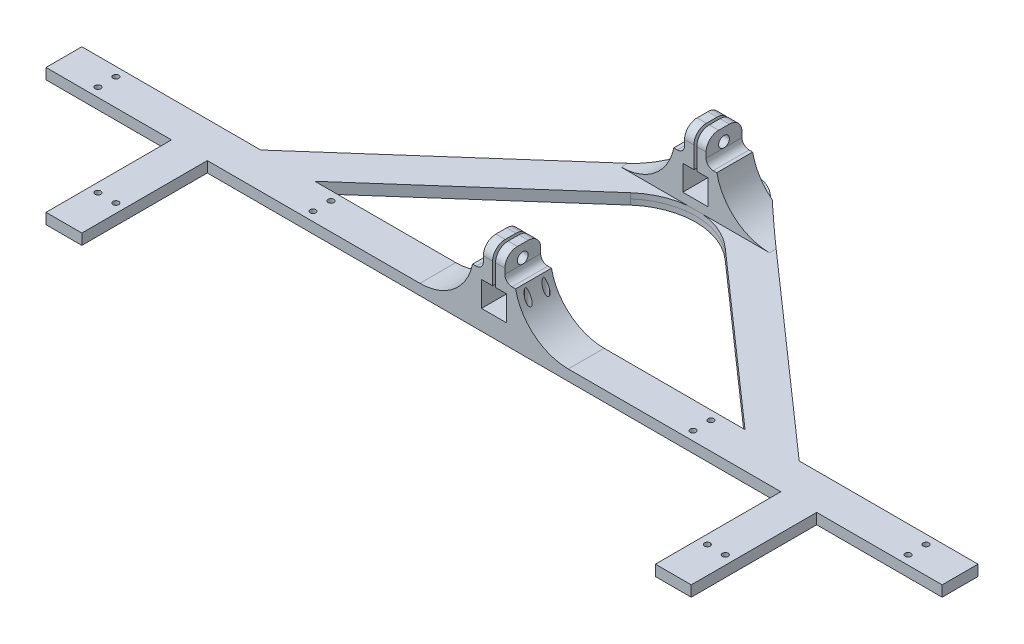
SolidWorks part; units mm, degrees
ref_plane "前视基准面" through (0, 0, 0) normal (0, 0, 1) x (1, 0, 0)
ref_plane "上视基准面" through (0, 0, 0) normal (0, 1, 0) x (1, 0, 0)
ref_plane "右视基准面" through (0, 0, 0) normal (1, 0, 0) x (0, 0, -1)
sketch "草图1" plane through (0, 0, 0) normal (0, 1, 0) x (1, 0, 0)
  line L1 (-125, 5) -> (125, 5)
  line L2 (-125, 5) -> (-125, -5)
  line L3 (-125, -5) -> (125, -5)
  line L4 (125, 5) -> (125, -5)
  line L5 (-125, 5) -> (125, -5) construction
  line L6 (-125, -5) -> (125, 5) construction
  point P0 (0, 0)
  dimension "D1" = 250
  dimension "D2" = 10
extrude "凸台-拉伸1" add sketch "草图1" along normal blind 1.5
sketch "草图22" plane through (0, 0, 0) normal (0, -1, 0) x (1, 0, 0)
  line L0 (0, 107.0541) -> (0, -222.8841) construction
  line L1 (0, 0) -> (-60, 0)
  line L2 (-125, 5) -> (125, 5) construction
  line L4 (125, -5) -> (-125, -5) construction
  line L5 (60, 0) -> (60, -5)
  line L6 (-60, -5) -> (0, -57.915)
  line L7 (0, -57.915) -> (60, -5)
  line L8 (-75.1186, -5) -> (0, -71.2484)
  line L9 (0, -71.2484) -> (75.1186, -5)
  line L10 (-60, -5) -> (-75.1186, -5)
  line L11 (60, -5) -> (75.1186, -5)
  line M16 (-125, -5) -> (125, -5)
  dimension "D1" = 60
  dimension "D2" = 80
  dimension "D3" = 10
extrude "凸台-拉伸10" add sketch "草图22" against normal blind 1.5 separate body contours L0 L6 L8 M16 | L7 L0 L9 M16 region at (33.9206, 0, -34.9152) region at (-33.9206, 0, -34.9152)
fillet "圆角1" radius 10 1 edges at (0, 0.75, -71.2484)
fillet "圆角2" radius 20 1 edges at (0, 0.75, -57.915)
sketch "草图24" plane through (0, 1.5, 0) normal (0, 1, 0) x (1, 0, 0)
  line L1 (-10, 5) -> (10, 5)
  line L2 (-10, 5) -> (-10, -5)
  line L3 (-10, -5) -> (10, -5)
  line L4 (10, 5) -> (10, -5)
  line L5 (-10, 5) -> (10, -5) construction
  line L6 (-10, -5) -> (10, 5) construction
  point P0 (0, 0)
  dimension "D1" = 20
  dimension "D2" = 10
extrude "凸台-拉伸11" add sketch "草图24" along normal blind 20
sketch "草图25" plane through (0, 0, 5) normal (0, 0, 1) x (1, 0, 0)
  line L1 (0, 23.6125) -> (0, -2.2867) construction
sketch "草图26" plane through (0, 1.5, 0) normal (0, 1, 0) x (1, 0, 0)
  line L0 (0, 141.3842) -> (0, -41.294) construction
  line L2 (-11, 61.1419) -> (11, 61.1419)
  line L3 (-11, 61.1419) -> (-11, 51.1419)
  line L4 (-11, 51.1419) -> (11, 51.1419)
  line L5 (11, 61.1419) -> (11, 51.1419)
  line L6 (-11, 61.1419) -> (11, 51.1419) construction
  line L7 (-11, 51.1419) -> (11, 61.1419) construction
  point P6 (0, 56.1419)
  dimension "D1" = 22
  dimension "D2" = 10
sketch "草图41" plane through (0, 0, 5) normal (0, 0, 1) x (1, 0, 0)
  line L0 (125, 0.75) -> (-129.8236, 0.75) construction
  line L1 (125, 1.5) -> (125, 0) construction
  line L2 (125, 0.75) -> (85, 0.75)
  line L4 (80, 1.5) -> (90, 1.5)
  line L5 (80, 1.5) -> (80, 0)
  line L6 (80, 0) -> (90, 0)
  line L7 (90, 1.5) -> (90, 0)
  line L8 (80, 1.5) -> (90, 0) construction
  line L9 (80, 0) -> (90, 1.5) construction
  line M8 (-125, 0) -> (125, 0)
  line M10 (125, 1.5) -> (10, 1.5)
  dimension "D1" = 40
  dimension "D2" = 10
  dimension "D3" = 1.5
extrude "凸台-拉伸13" add sketch "草图41" along normal blind 35 contours L7 L5 M10 M8 region at (85, 1.3989, 5)
sketch "草图42" plane through (0, 0, 5) normal (0, 0, 1) x (1, 0, 0)
  line L0 (-125, 0.75) -> (-85, 0.75)
  line L1 (-125, 1.5) -> (-125, 0) construction
  line L3 (-90, 1.5) -> (-80, 1.5)
  line L4 (-90, 1.5) -> (-90, 0)
  line L5 (-90, 0) -> (-80, 0)
  line L6 (-80, 1.5) -> (-80, 0)
  line L7 (-90, 1.5) -> (-80, 0) construction
  line L8 (-90, 0) -> (-80, 1.5) construction
  line M14 (-10, 1.5) -> (-125, 1.5)
  line M16 (-125, 0) -> (80, 0)
  dimension "D1" = 40
  dimension "D2" = 10
  dimension "D3" = 1.5
extrude "凸台-拉伸14" add sketch "草图42" along normal blind 35 contours L6 L4 M14 M16 region at (-85, 1.3989, 5)
sketch "草图57" plane through (0, 0, 0) normal (0, -1, 0) x (-1, 0, 0)
  line L0 (125, -5) -> (90, -5)
  line L1 (90, -5) -> (90, -40)
  line L2 (90, -40) -> (80, -40)
  line L3 (80, -40) -> (80, -5)
  line L4 (80, -5) -> (-80, -5)
  line L5 (-80, -5) -> (-80, -40)
  line L6 (-80, -40) -> (-90, -40)
  line L7 (-90, -40) -> (-90, -5)
  line L8 (-90, -5) -> (-125, -5)
  line L9 (-125, -5) -> (-125, 5)
  line L10 (-125, 5) -> (-75.1186, 5)
  line L11 (-75.1186, 5) -> (-6.6144, 65.415)
  line L12 (-6.6144, 65.415) -> (0, 71.2484)
  line L13 (0, 71.2484) -> (6.6144, 65.415)
  line L14 (6.6144, 65.415) -> (75.1186, 5)
  line L15 (75.1186, 5) -> (125, 5)
  line L16 (125, 5) -> (125, -5)
  line L17 (60, 5) -> (-60, 5)
  line L18 (-60, 5) -> (0, 57.915)
  line L19 (0, 57.915) -> (60, 5)
extrude "凸台-拉伸15" add sketch "草图57" along normal blind 1.5
fillet "圆角5" radius 20 1 edges at (0, -0.75, -57.915)
fillet "圆角6" radius 10 1 edges at (0, -0.75, -71.2484)
sketch "草图58" plane through (0, -1.5, 0) normal (0, -1, 0) x (1, 0, 0)
  line L0 (0, 12.1149) -> (0, -11.1082) construction
  line L1 (0, 0) -> (7, 0)
  line L2 (7, 0) -> (7, 2.5)
  line L3 (7, 0) -> (7, -2.5)
  line L4 (127.0686, 0) -> (101.0767, 0) construction
  line L5 (125, 0) -> (113, 0)
  line L6 (125, -5) -> (125, 5) construction
  line L7 (113, 0) -> (113, 2.5)
  line L8 (113, 0) -> (113, -2.5)
  line L10 (-125, 5) -> (-125, -5)
  line L11 (125, 5) -> (125, -5)
  line L12 (0, 0) -> (53, 0)
  line L14 (53, 0) -> (53, 2.5)
  line L15 (53, 0) -> (53, -2.5)
  line L16 (-85, 40) -> (-85, 28)
  line L17 (-80, 40) -> (-90, 40) construction
  line L18 (-85, 28) -> (-87.5, 28)
  line L19 (-85, 28) -> (-82.5, 28)
  circle A0 centre (7, -2.5) radius 0.8
  circle A1 centre (7, 2.5) radius 0.8
  circle A2 centre (113, 2.5) radius 0.8
  circle A3 centre (113, -2.5) radius 0.8
  circle A4 centre (-113, -2.5) radius 0.8
  circle A5 centre (-113, 2.5) radius 0.8
  circle A6 centre (53, 2.5) radius 0.8
  circle A7 centre (53, -2.5) radius 0.8
  circle A8 centre (-53, -2.5) radius 0.8
  circle A9 centre (-53, 2.5) radius 0.8
  circle A10 centre (-82.5, 28) radius 0.8
  circle A11 centre (-87.5, 28) radius 0.8
  circle A12 centre (82.5, 28) radius 0.8
  circle A13 centre (87.5, 28) radius 0.8
  dimension "D4" = 1.6
  dimension "D5" = 1.6
  dimension "D9" = 1.6
  dimension "D10" = 1.6
  dimension "D15" = 1.6
  dimension "D16" = 1.6
  dimension "D20" = 1.6
  dimension "D21" = 1.6
  dimension "D1" = 7
  dimension "D2" = 2.5
  dimension "D3" = 2.5
  dimension "D6" = 12
  dimension "D7" = 2.5
  dimension "D8" = 2.5
  dimension "D11" = 250
  dimension "D12" = 53
  dimension "D13" = 2.5
  dimension "D14" = 2.5
  dimension "D17" = 12
  dimension "D18" = 2.5
  dimension "D19" = 2.5
extrude "切除-拉伸52" cut sketch "草图58" against normal through all contours A5 | A4 | A11 | A10 | A9 | A8 | A0 | A1 | A6 | A7 | A2 | A3 | A12 | A13 region at (6.4503, -1.5, 3.0497) region at (7.5497, -1.5, -1.9503) region at (52.4503, -1.5, 3.0497) region at (53.5497, -1.5, -1.9503) region at (112.4503, -1.5, 3.0497) region at (113.5497, -1.5, -1.9503) region at (-88.2774, -1.5, 28) region at (-82.5, -1.5, 28.7774) region at (-113, -1.5, -2.5) region at (-113, -1.5, 2.5) region at (-53, -1.5, -2.5) region at (-53, -1.5, 2.5) region at (82.5, -1.5, 28) region at (87.5, -1.5, 28)
extrude "凸台-拉伸16" add sketch "草图26" along normal blind 20
sketch "草图59" plane through (0, 0, -61.1419) normal (0, 0, -1) x (-1, 0, 0)
  line L0 (0, 1.5376) -> (0, 4.0376)
  line L1 (0, 23.6125) -> (0, -2.2867) construction
  line L2 (0, 4.0376) -> (3.5, 4.0376)
  line L3 (3.5, 4.0376) -> (3.5, 11.0376)
  line L4 (3.5, 11.0376) -> (-3.5, 11.0376)
  line L5 (-3.5, 11.0376) -> (-3.5, 4.0376)
  line L6 (-3.5, 4.0376) -> (0, 4.0376)
  line L7 (0, 1.5376) -> (6, 1.5)
  line L8 (-11, 1.5) -> (11, 1.5) construction
  line L9 (6, 1.5) -> (6, 13.5)
  line L10 (6, 13.5) -> (-6, 13.5)
  line L11 (-6, 13.5) -> (-6, 1.5)
  line L12 (-6, 1.5) -> (0, 1.5376)
  line L14 (0, 13.5) -> (3, 13.5)
  line L18 (0, 13.5) -> (-3, 13.5)
  line L24 (0, 11.0376) -> (0.9278, 11.0376)
  line L26 (0, 13.5) -> (0.4, 13.5)
  line L27 (0, 13.5) -> (0, 20.5)
  line L28 (0, 20.5) -> (0.4, 20.5)
  line L29 (0.4, 13.5) -> (0.4, 20.5)
  line L30 (0, 13.5) -> (-0.4, 13.5)
  line L31 (0, 13.5) -> (0, 20.5)
  line L32 (0, 20.5) -> (-0.4, 20.5)
  line L33 (-0.4, 13.5) -> (-0.4, 20.5)
  line L34 (-0.4, 13.5) -> (0.4, 13.5)
  line L35 (-0.4, 13.5) -> (-0.4, 11.0376)
  line L36 (-0.4, 11.0376) -> (0.4, 11.0376)
  line L37 (0.4, 13.5) -> (0.4, 11.0376)
  line L38 (0, 13.5) -> (3, 13.5)
  line L39 (0, 13.5) -> (0, 20.5)
  line L40 (0, 20.5) -> (3, 20.5)
  line L41 (3, 13.5) -> (3, 20.5)
  line L42 (0, 13.5) -> (-3, 13.5)
  line L43 (0, 13.5) -> (0, 20.5)
  line L44 (0, 20.5) -> (-3, 20.5)
  line L45 (-3, 13.5) -> (-3, 20.5)
  line M21 (-11, 1.5) -> (11, 1.5)
  line M22 (11, 1.5) -> (11, 21.5)
  line M23 (11, 21.5) -> (-11, 21.5)
  line M24 (-11, 21.5) -> (-11, 1.5)
  dimension "D1" = 2.5
  dimension "D2" = 3.5
  dimension "D3" = 7
  dimension "D4" = 7
  dimension "D5" = 12
  dimension "D6" = 12
  dimension "D7" = 6
  dimension "D8" = 0.4
  dimension "D9" = 7
  dimension "D10" = 0.4
  dimension "D11" = 7
  dimension "D12" = 3
  dimension "D13" = 3
extrude "切除-拉伸53" cut sketch "草图59" against normal through all contours L10 L45 L44 L32 L28 L40 L41 L9 L11 M21 M22 M23 M24 | L5 L6 L2 L3 L4 L24 | L37 L14 L10 L35 L4 L24 | L33 L10 L27 L32 | L14 L29 L28 L27 region at (0, 7.5376, -61.1419) region at (-6.2973, 7.5, -61.1419) region at (0, 12.2688, -61.1419) region at (-0.2, 17, -61.1419) region at (0.2, 17, -61.1419)
fillet "圆角7" radius 15 2 edges at (6, 1.5, -56.1419) (-6, 1.5, -56.1419)
fillet "圆角8" radius 15 2 edges at (6, 1.5, 0) (-6, 1.5, 0)
fillet "圆角9" radius 3.5 8 edges at (-1.7, 20.5, 5) (1.7, 20.5, 5) (1.7, 20.5, -5) (-1.7, 20.5, -5) (-1.7, 20.5, -51.1419) (1.7, 20.5, -51.1419) (-1.7, 20.5, -61.1419) (1.7, 20.5, -61.1419)
sketch "草图60" plane through (-3, 0, 0) normal (-1, 0, 0) x (0, 0, 1)
  line L0 (-56.1419, 20.5) -> (-56.1419, 17) construction
  line L1 (-54.6419, 20.5) -> (-57.6419, 20.5) construction
  circle A0 centre (-56.1419, 17) radius 1.5
  dimension "D2" = 3
  dimension "D1" = 3.5
extrude "切除-拉伸54" cut sketch "草图60" against normal through all
sketch "草图61" plane through (-3, 0, 0) normal (-1, 0, 0) x (0, 0, 1)
  line L0 (0, 20.5) -> (0, 17) construction
  line L1 (1.5, 20.5) -> (-1.5, 20.5) construction
  circle A0 centre (0, 17) radius 1.5
  dimension "D2" = 3
  dimension "D1" = 3.5
extrude "切除-拉伸55" cut sketch "草图61" against normal through all
fillet "圆角10" radius 2 4 edges at (3, 13.5, -56.1419) (3, 13.5, 0) (-3, 13.5, 0) (-3, 13.5, -56.1419)
